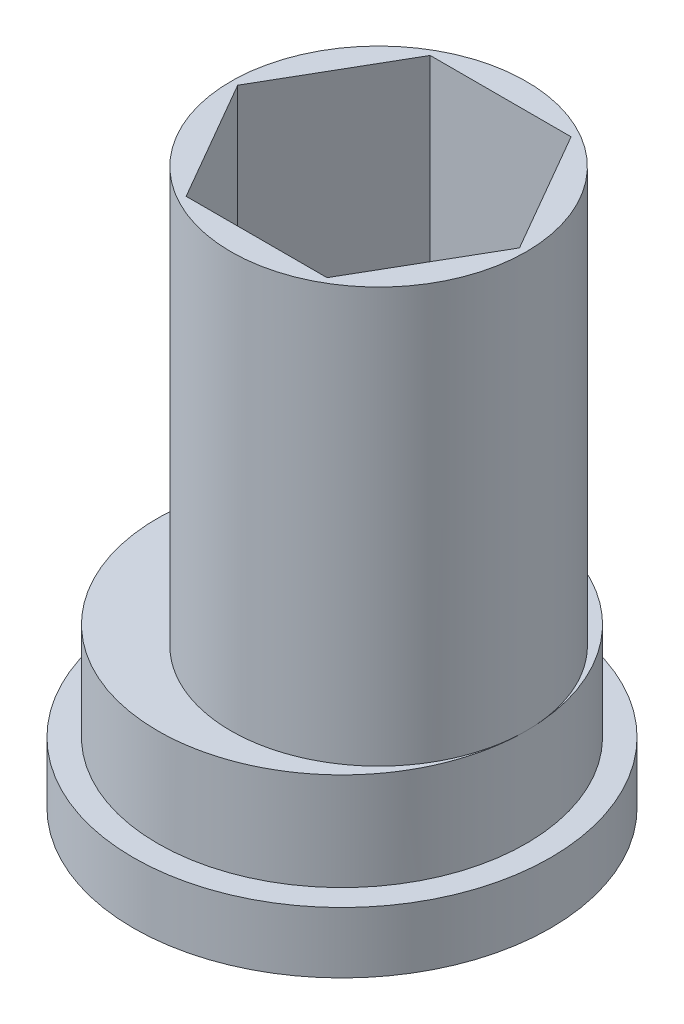
SolidWorks part; units mm, degrees
ref_plane "Front Plane" through (0, 0, 0) normal (0, 0, 1) x (1, 0, 0)
ref_plane "Top Plane" through (0, 0, 0) normal (0, 1, 0) x (1, 0, 0)
ref_plane "Right Plane" through (0, 0, 0) normal (1, 0, 0) x (0, 0, -1)
sketch "Sketch1" plane through (0, 0, 0) normal (0, 1, 0) x (1, 0, 0)
  line L0 (0, 0) -> (-1.5, 0) construction
  line L1 (5.7735, 0) -> (2.8868, 5)
  line L2 (2.8868, 5) -> (-2.8868, 5)
  line L3 (-2.8868, 5) -> (-5.7735, 0)
  line L4 (-5.7735, 0) -> (-2.8868, -5)
  line L5 (-2.8868, -5) -> (2.8868, -5)
  line L6 (2.8868, -5) -> (5.7735, 0)
  circle A0 centre (0, 0) radius 5 construction
  circle A1 centre (0, 0) radius 6.05
  circle A2 centre (-1.5, 0) radius 7.55
  circle A3 centre (-1.5, 0) radius 8.55
  point P13 (0, 0)
  dimension "D1" = 12.1
  dimension "D2" = 15.1
  dimension "D4" = 17.1
  dimension "D3" = 10
  dimension "D5" = 1.5
extrude "Boss-Extrude1" add sketch "Sketch1" against normal blind 4 contours A1 L6 L5 L4 L3 L2 L1 | A1 A2 region at (-5.8789, 0, 0) region at (-8.8365, 0, 0)
extrude "Boss-Extrude2" add sketch "Sketch1<4>" against normal blind 2.5 from surface contours A1 A2 | A1 L6 L5 L4 L3 L2 L1 | A3 A2 region at (-5.8789, 0, 0) region at (-8.8365, 0, 0) region at (-9.8082, 0, 0) starting at face at (0, -4, 0)
sketch "Sketch1<4>" plane through (0, 0, 0) normal (0, 1, 0) x (1, 0, 0) same geometry as "Sketch1"
extrude "Boss-Extrude3" add sketch "Sketch1<5>" along normal blind 17 contours A1 L6 L5 L4 L3 L2 L1 region at (-5.8789, 0, 0)
sketch "Sketch1<5>" plane through (0, 0, 0) normal (0, 1, 0) x (1, 0, 0) same geometry as "Sketch1"
